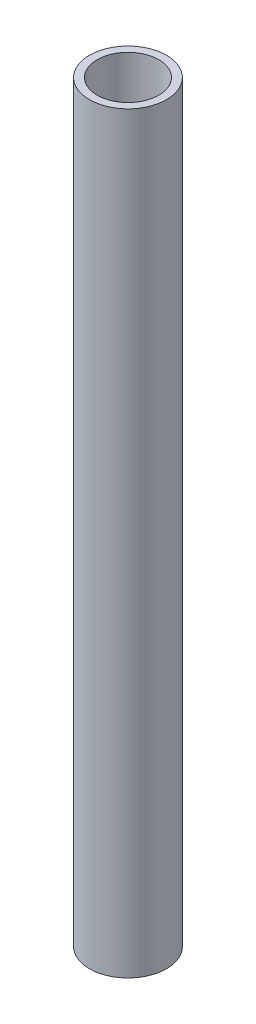
SolidWorks part; units mm, degrees
ref_plane "Front Plane" through (0, 0, 0) normal (0, 0, 1) x (1, 0, 0)
ref_plane "Top Plane" through (0, 0, 0) normal (0, 1, 0) x (1, 0, 0)
ref_plane "Right Plane" through (0, 0, 0) normal (1, 0, 0) x (0, 0, -1)
sketch "Sketch1" plane through (0, 0, 0) normal (0, 1, 0) x (1, 0, 0)
  circle A0 centre (0, 0) radius 10
  circle A1 centre (0, 0) radius 8
  dimension "D1" = 20
  dimension "D2" = 2
extrude "Boss-Extrude1" add sketch "Sketch1" along normal blind 195.4715
